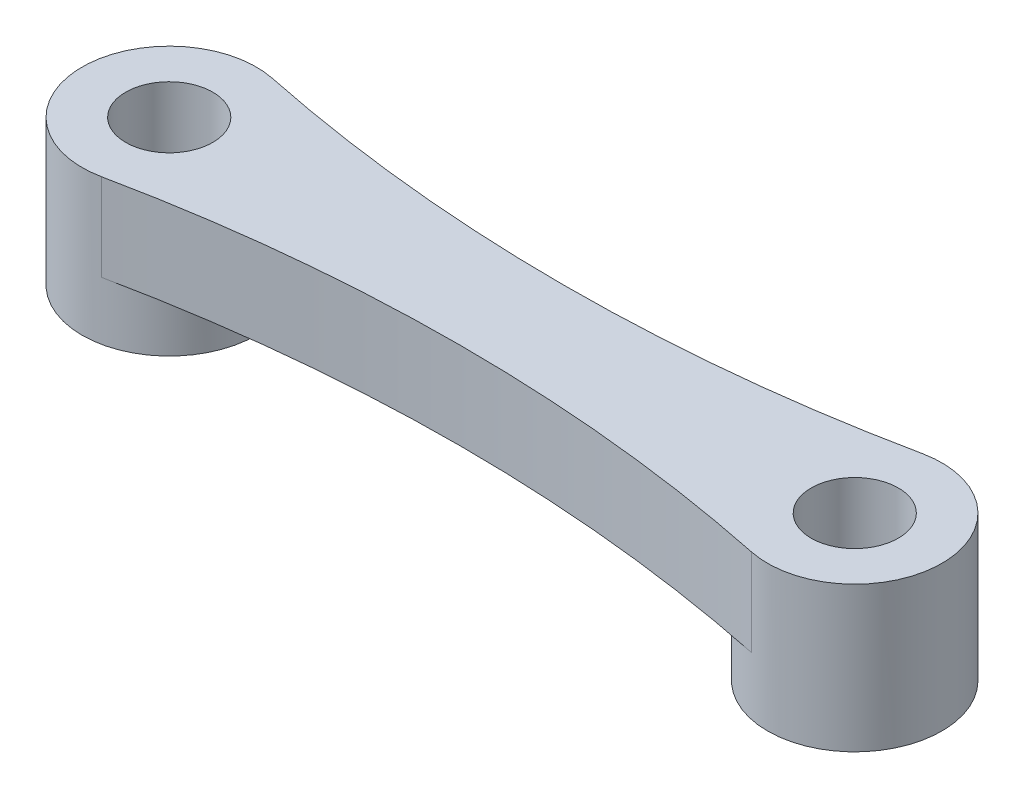
SolidWorks part; units mm, degrees
ref_plane "Front Plane" through (0, 0, 0) normal (0, 0, 1) x (1, 0, 0)
ref_plane "Top Plane" through (0, 0, 0) normal (0, 1, 0) x (1, 0, 0)
ref_plane "Right Plane" through (0, 0, 0) normal (1, 0, 0) x (0, 0, -1)
sketch "Sketch1" plane through (0, 0, 0) normal (0, 1, 0) x (1, 0, 0)
  line L0 (-11.8, 0) -> (11.8, 0) construction
  line L1 (-11.8, 3) -> (11.8, 3)
  line L2 (-11.8, -3) -> (11.8, -3)
  circle A0 centre (-11.8, 0) radius 1.5
  circle A1 centre (11.8, 0) radius 1.5
  arc A2 (-11.8, 3) -> (-11.8, -3) centre (-11.8, 0) ccw
  arc A3 (11.8, -3) -> (11.8, 3) centre (11.8, 0) ccw
  point P4 (0, 0)
  dimension "D2" = 3
  dimension "D3" = 3
  dimension "D4" = 6
  dimension "D5" = 6
  dimension "D1" = 23.6
extrude "Boss-Extrude1" add sketch "Sketch1" along normal blind 3
sketch "Sketch2" plane through (0, 3, 0) normal (0, 1, 0) x (1, 0, 0)
  line L0 (-11.8, 0) -> (11.8, 0) construction
  arc A0 (-11.1897, 2.9373) -> (-11.1897, -2.9373) centre (-11.8, 0) ccw
  arc A1 (11.1897, -2.9373) -> (11.1897, 2.9373) centre (11.8, 0) ccw
  arc A2 (-11.1897, 2.9373) -> (11.1897, 2.9373) centre (0, 56.787) ccw
  arc A3 (-11.8, 3) -> (-11.8, -3) centre (-11.8, 0) ccw construction
  arc A4 (11.8, -3) -> (11.8, 3) centre (11.8, 0) ccw construction
  arc A5 (-11.1897, -2.9373) -> (11.1897, -2.9373) centre (0, -56.787) cw
  dimension "D1" = 55
extrude "Cut-Extrude1" cut sketch "Sketch2" against normal through all flip side to cut
sketch "Sketch3" plane through (0, 3, 0) normal (0, 1, 0) x (1, 0, 0)
  circle A0 centre (-11.8, 0) radius 3
  circle A1 centre (11.8, 0) radius 3
  arc A2 (-11.1897, 2.9373) -> (-11.1897, -2.9373) centre (-11.8, 0) ccw construction
  arc A3 (11.1897, -2.9373) -> (11.1897, 2.9373) centre (11.8, 0) ccw construction
  circle A4 centre (11.8, 0) radius 1.5 construction
  circle A5 centre (-11.8, 0) radius 1.5 construction
  circle A6 centre (11.8, 0) radius 1.5
  circle A7 centre (-11.8, 0) radius 1.5
  circle M1 centre (-11.8, 0) radius 1.5
  circle M2 centre (11.8, 0) radius 1.5
  arc M3 (11.1897, -2.9373) -> (11.1897, 2.9373) centre (11.8, 0) ccw
  arc M5 (-11.1897, 2.9373) -> (-11.1897, -2.9373) centre (-11.8, 0) ccw
extrude "Boss-Extrude2" add sketch "Sketch3" against normal blind 2 from surface contours A0 M5 M1 | A1 M3 M2 region at (-9.5387, 3, 1.8397) region at (13.6397, 3, 2.2613) starting at face at (-11.8, 0, 1.5)
